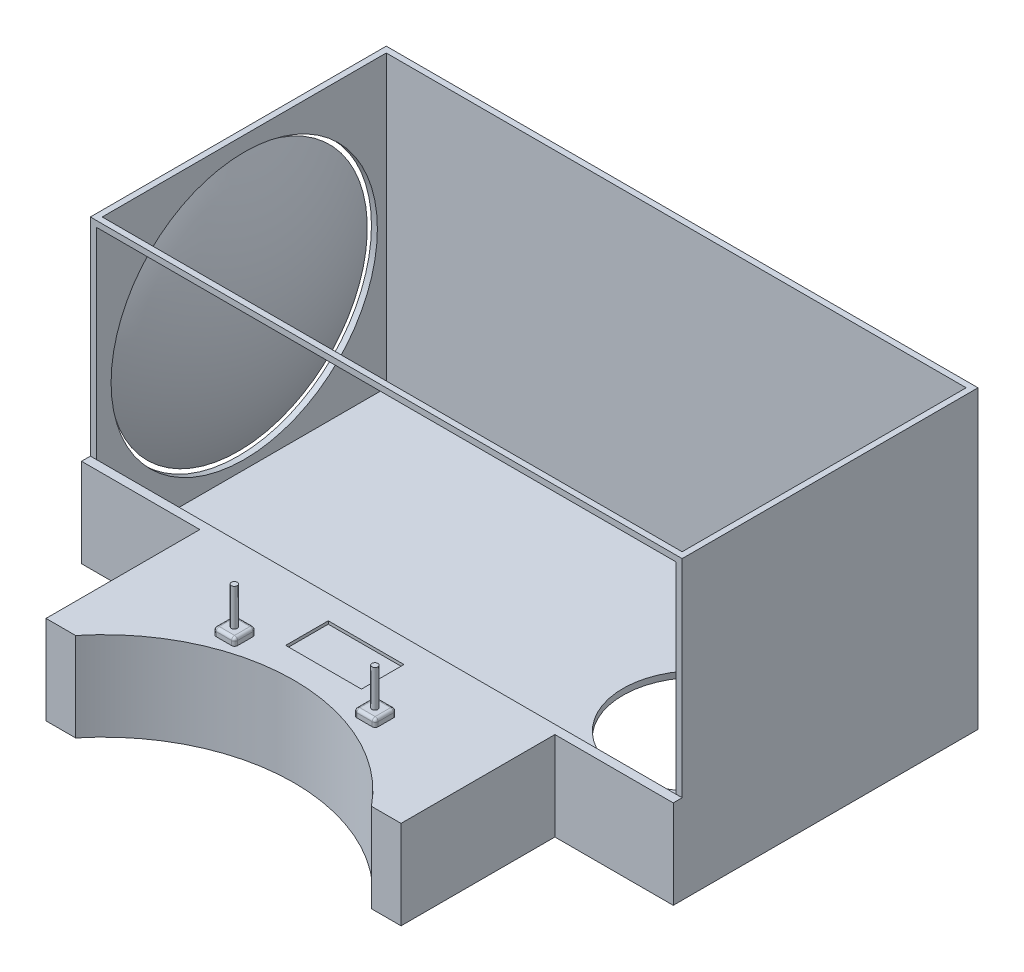
SolidWorks part; units mm, degrees
ref_plane "前视基准面" through (0, 0, 0) normal (0, 0, 1) x (1, 0, 0)
ref_plane "上视基准面" through (0, 0, 0) normal (0, 1, 0) x (1, 0, 0)
ref_plane "右视基准面" through (0, 0, 0) normal (1, 0, 0) x (0, 0, -1)
sketch "草图2" plane through (0, 0, 0) normal (0, 1, 0) x (1, 0, 0)
  line L0 (0, 1123.0854) -> (0, -966.4475) construction
  line L1 (-3007.7512, 0) -> (3035.7632, 0) construction
  line L3 (-1000, 500) -> (1000, 500)
  line L4 (-1000, 500) -> (-1000, -500)
  line L5 (-1000, -500) -> (1000, -500)
  line L6 (1000, 500) -> (1000, -500)
  dimension "D1" = 2000
  dimension "D2" = 1000
extrude "凸台-拉伸1" add sketch "草图2" along normal blind 500 and the other way blind 500
sketch "草图3" plane through (0, 500, 0) normal (0, 1, 0) x (1, 0, 0)
  line L0 (1000, 500) -> (-1000, 500) construction
  line L1 (-980, 480) -> (980, 480)
  line L2 (-980, 480) -> (-980, -480)
  line L3 (-980, -480) -> (980, -480)
  line L4 (980, 480) -> (980, -480)
  line L5 (-1000, -500) -> (1000, -500) construction
  line L6 (1000, -500) -> (1000, 500) construction
  line L7 (-1000, 500) -> (-1000, -500) construction
  dimension "D1" = 20
  dimension "D2" = 20
  dimension "D3" = 20
  dimension "D4" = 20
extrude "切除-拉伸1" cut sketch "草图3" against normal blind 980
sketch "草图4" plane through (0, 0, 500) normal (0, 0, 1) x (1, 0, 0)
  line L0 (-1000, 500) -> (1000, 500) construction
  line L1 (-980, 480) -> (980, 480)
  line L2 (-980, 480) -> (-980, -480)
  line L3 (-980, -480) -> (980, -480)
  line L4 (980, 480) -> (980, -480)
  line L5 (-1000, -500) -> (1000, -500) construction
  line L6 (-1000, -500) -> (-1000, 500) construction
  line L7 (1000, -500) -> (1000, 500) construction
  dimension "D1" = 20
  dimension "D2" = 20
  dimension "D3" = 20
  dimension "D4" = 20
extrude "切除-拉伸2" cut sketch "草图4" against normal blind 100
sketch "草图5" plane through (-1000, 0, 0) normal (-1, 0, 0) x (0, 0, 1)
  circle A0 centre (0, 0) radius 450
extrude "切除-拉伸3" cut sketch "草图5" against normal blind 100
sketch "草图6" plane through (0, 0, 0) normal (0, 1, 0) x (1, 0, 0)
  line L0 (-900, 0) -> (-2900, 0)
  arc A1 (-2900, 0) -> (-900, 0) centre (-1900, 0) cw
  dimension "D1" = 1900
sketch "草图7" plane through (0, 0, 0) normal (0, 1, 0) x (1, 0, 0)
  line L0 (-896.1777, 0) -> (1164.9666, 0) construction
  point P3 (-1283.2853, 0)
  point P4 (1164.9666, 0)
  point P5 (-896.1777, 0)
  point P6 (0, 0)
revolve "旋转4" add sketch "草图6" angle 360 about L0
sketch "草图8" plane through (-1000, 0, 0) normal (-1, 0, 0) x (0, 0, 1)
  circle A0 centre (0, 0) radius 1000
extrude "切除-拉伸4" cut sketch "草图8" along normal blind 1900
sketch "草图9" plane through (0, 0, 500) normal (0, 0, 1) x (1, 0, 0)
  line L0 (1000, -500) -> (1000, 500) construction
  line L1 (-1000, -500) -> (1000, -500)
  line L2 (-1000, -500) -> (-1000, -200)
  line L3 (-1000, -200) -> (1000, -200)
  line L4 (1000, -500) -> (1000, -200)
  dimension "D1" = 300
extrude "凸台-拉伸2" add sketch "草图9" along normal blind 300
sketch "草图10" plane through (0, -500, 0) normal (0, -1, 0) x (1, 0, 0)
  line L0 (-1000, 800) -> (-1000, 1050)
  line L1 (-1000, 1050) -> (-500, 1050)
  line L2 (1000, 800) -> (1000, 1050)
  line L3 (1000, 1050) -> (500, 1050)
  line L4 (-1000, 800) -> (1000, 800)
  arc A0 (-500, 1050) -> (500, 1050) centre (0, 1455.7813) ccw
  dimension "D1" = 250
  dimension "D2" = 250
  dimension "D3" = 500
  dimension "D4" = 500
extrude "凸台-拉伸3" add sketch "草图10" against normal blind 300 contours L1 A0 L3 L2 L4 L0
sketch "草图11" plane through (0, -200, 0) normal (0, 1, 0) x (1, 0, 0)
  line L0 (0, 677.658) -> (17.9075, -1197.9455) construction
sketch "草图12" plane through (0, -200, 0) normal (0, 1, 0) x (1, 0, 0)
  line L4 (12.0076, -580) -> (12.0076, -500)
  line L5 (980, -500) -> (-980, -500) construction
  line L7 (0, 677.658) -> (17.9075, -1197.9455) construction
  line L8 (12.0076, -580) -> (140.0076, -580)
  line L9 (140.0076, -580) -> (140.0076, -724)
  line L10 (140.0076, -724) -> (-115.9924, -724)
  line L11 (-115.9924, -724) -> (-115.9924, -580)
  line L12 (-115.9924, -580) -> (12.0076, -580)
extrude "切除-拉伸5" cut sketch "草图12" against normal blind 10 contours L12 L8 L9 L10 L11
sketch "草图14" plane through (0, -200, 0) normal (0, 1, 0) x (1, 0, 0)
  line L0 (0, 677.658) -> (17.9075, -1197.9455) construction
  line L1 (-268.4985, -744) -> (-196.4985, -744)
  line L2 (-268.4985, -744) -> (-268.4985, -816)
  line L3 (-268.4985, -816) -> (-196.4985, -816)
  line L4 (-196.4985, -744) -> (-196.4985, -816)
  line L5 (206.5312, -744) -> (278.5312, -744)
  line L6 (206.5312, -744) -> (206.5312, -816)
  line L7 (206.5312, -816) -> (278.5312, -816)
  line L8 (278.5312, -744) -> (278.5312, -816)
  line L9 (140.0076, -724) -> (-115.9924, -724) construction
  dimension "D1" = 72
  dimension "D2" = 72
  dimension "D3" = 72
  dimension "D4" = 72
  dimension "D5" = 0.547
  dimension "D6" = 20
  dimension "D7" = 20
extrude "凸台-拉伸4" add sketch "草图14" along normal blind 25
fillet "圆角1" radius 10 16 edges at (278.5312, -187.5, 744) (206.5312, -187.5, 744) (278.5312, -187.5, 816) (242.5312, -175, 744) (206.5312, -187.5, 816) (278.5312, -175, 780) (242.5312, -175, 816) (206.5312, -175, 780) (-196.4985, -187.5, 744) (-268.4985, -187.5, 744) (-268.4985, -187.5, 816) (-196.4985, -187.5, 816) (-232.4985, -175, 744) (-196.4985, -175, 780) (-268.4985, -175, 780) (-232.4985, -175, 816)
sketch "草图15" plane through (0, -175, 0) normal (0, 1, 0) x (1, 0, 0)
  line L1 (-258.4985, -816) -> (-206.4985, -816) construction
  line L3 (268.5312, -816) -> (216.5312, -816) construction
  circle A0 centre (242.5015, -781) radius 10
  circle A1 centre (-232.4985, -781) radius 10
  point P4 (0, 0)
  dimension "D1" = 35
  dimension "D2" = 35
  dimension "D3" = 475
extrude "凸台-拉伸5" add sketch "草图15" along normal blind 125
sketch "草图16" plane through (0, -480, 0) normal (0, 1, 0) x (1, 0, 0)
  line L0 (-896.1777, 0) -> (1164.9666, 0) construction
  circle A0 centre (550, 0) radius 250
extrude "切除-拉伸6" cut sketch "草图16" against normal blind 125 contours A0
sketch "草图17" plane through (0, -500, 0) normal (0, -1, 0) x (1, 0, 0)
  line L0 (-896.1777, 0) -> (1164.9666, 0) construction
  line L2 (0, -677.658) -> (17.9075, 1197.9455) construction
  line L3 (14.0126, 790) -> (313.153, 790)
  line L4 (313.153, 790) -> (313.153, 550)
  line L5 (313.153, 550) -> (-286.847, 550)
  line L6 (-286.847, 550) -> (-286.847, 790)
  line L7 (-286.847, 790) -> (14.0126, 790)
  dimension "D1" = 550
  dimension "D2" = 240
  dimension "D3" = 600
extrude "切除-拉伸7" cut sketch "草图17" against normal blind 280
sketch "草图18" plane through (0, -200, 0) normal (0, 1, 0) x (1, 0, 0)
  line L4 (-1000, -1050) -> (-500, -1050) construction
  line L5 (-600, -1050) -> (-1000, -1050)
  line L7 (1000, -1050) -> (500, -1050) construction
  line L8 (1000, -1050) -> (1000, -500) construction
  line L9 (1000, -1050) -> (600, -1050)
  line L13 (-1000, -1050) -> (-1000, -530)
  line L14 (-1000, -1050) -> (-1000, -500) construction
  line L15 (-1000, -530) -> (-600, -530)
  line L16 (-600, -530) -> (-600, -1050)
  line L17 (600, -1050) -> (600, -530)
  line L18 (600, -530) -> (1000, -530)
  line L19 (1000, -530) -> (1000, -1050)
  point P1 (0, 0)
extrude "切除-拉伸9" cut sketch "草图18" against normal blind 344
sketch "草图19" plane through (-1000, 0, 0) normal (-1, 0, 0) x (0, 0, 1)
  circle A0 centre (0, 0) radius 200
extrude "切除-拉伸10" cut sketch "草图19" against normal blind 50
sketch "草图20" plane through (-950, 0, 0) normal (-1, 0, 0) x (0, 0, 1)
  circle A0 centre (0, 0) radius 100
extrude "切除-拉伸11" cut sketch "草图20" against normal blind 25
